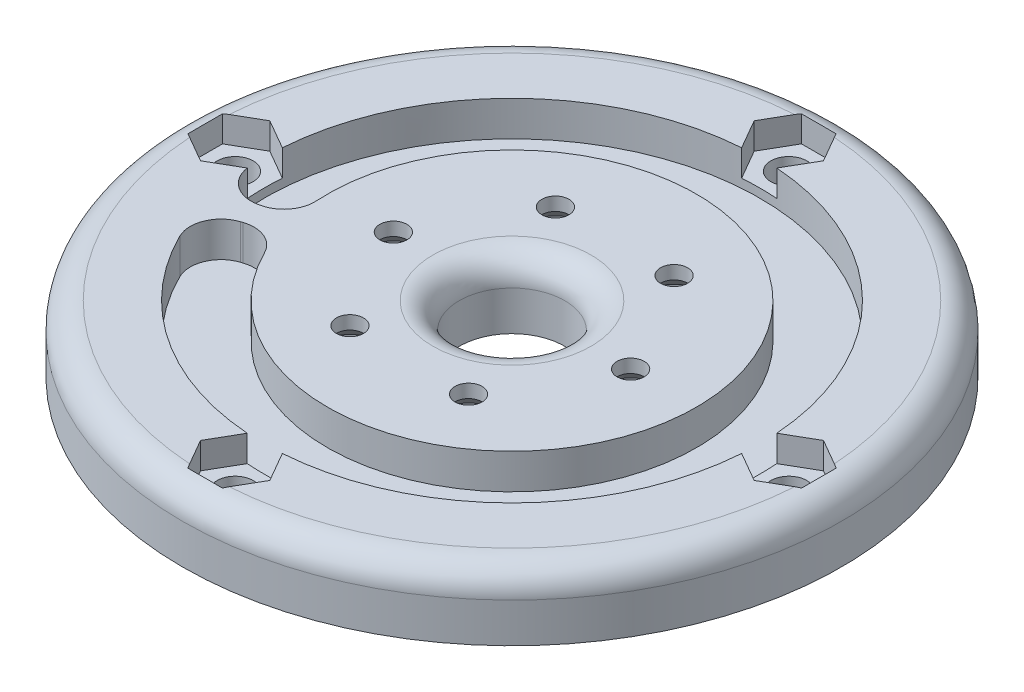
SolidWorks part; units mm, degrees
ref_plane "Front Plane" through (0, 0, 0) normal (0, 0, 1) x (1, 0, 0)
ref_plane "Top Plane" through (0, 0, 0) normal (0, 1, 0) x (1, 0, 0)
ref_plane "Right Plane" through (0, 0, 0) normal (1, 0, 0) x (0, 0, -1)
sketch "草图1" plane through (0, 0, 0) normal (0, 1, 0) x (1, 0, 0)
  circle A0 centre (0, 0) radius 37.5
  dimension "D1" = 75
extrude "凸台-拉伸1" add sketch "草图1" along normal blind 7.5
ref_axis "基准轴1" through (0, 7.5, 0) along (0, -1, 0)
sketch "草图2" plane through (0, 7.5, 0) normal (0, 1, 0) x (1, 0, 0)
  line L0 (0, 0) -> (-37.5, 0) construction
  circle A0 centre (0, 0) radius 37.5 construction
  circle A1 centre (-31.5, 0) radius 2.05
  dimension "D1" = 4.1
  dimension "D2" = 31.5
extrude "切除-拉伸1" cut sketch "草图2" against normal through all
sketch "草图3" plane through (0, 7.5, 0) normal (0, 1, 0) x (1, 0, 0)
  line L1 (-31.5, 3.944) -> (-34.9156, 1.972)
  line L2 (-34.9156, 1.972) -> (-34.9156, -1.972)
  line L3 (-34.9156, -1.972) -> (-31.5, -3.944)
  line L4 (-31.5, -3.944) -> (-28.0844, -1.972)
  line L5 (-28.0844, -1.972) -> (-28.0844, 1.972)
  line L6 (-28.0844, 1.972) -> (-31.5, 3.944)
  circle A0 centre (-31.5, 0) radius 3.4156 construction
  dimension "D1" = 3.944
extrude "切除-拉伸2" cut sketch "草图3" against normal blind 3
pattern_circular "阵列(圆周)1" count 4 over 360 about axis through (0, 7.5, 0) along (0, -1, 0) of "切除-拉伸2", "切除-拉伸1"
sketch "草图4" plane through (0, 0, 0) normal (0, -1, 0) x (1, 0, 0)
  line L0 (0, 0) -> (-31.5, 0) construction
  circle A0 centre (-13.5, 0) radius 3.05
  dimension "D1" = 13.5
  dimension "D2" = 6.1
extrude "切除-拉伸3" cut sketch "草图4" against normal offset from surface (4.5 mm away) 3 up to face at (0, 7.5, -31.5)
sketch "草图5" plane through (0, 4.5, 0) normal (0, -1, 0) x (1, 0, 0)
  line L0 (-31.5, 0) -> (0, 0) construction
  point P4 (-13.5, 0)
  dimension "D1" = 13.5
hole_wizard "CSK for M3 Countersunk Flat Head Screw1" positions "3D草图1" profile "草图6" countersink size "M3" standard "ISO" end condition through all
sketch3d "3D草图1"
  point P0 (-13.5, 4.5, 0)
sketch "草图6" plane through (-13.5, 4.5, 0) normal (1, 0, 0) x (0, 0, -1)
  line L0 (0, 0) -> (0, 3)
  line L1 (0, 3) -> (1.54, 3)
  line L2 (1.54, 3) -> (1.54, 1.48)
  line L3 (1.54, 1.48) -> (3.02, 0)
  line L5 (3.02, 0) -> (0, 0)
  line L6 (-1.54, 1.48) -> (-3.02, 0) construction
  line L11 (0, -6.35) -> (0, 107.95) construction
  dimension "Thru Hole Dia." = 3.08
  dimension "Thru Hole Depth" = 3
  dimension "Near C'Sink Dia." = 6.04
  dimension "Near C'Sink Angle" = 90
pattern_circular "阵列(圆周)2" count 6 every 60 about axis through (0, 7.5, 0) along (0, -1, 0) of "CSK for M3 Countersunk Flat Head Screw1", "切除-拉伸3"
sketch "草图7" plane through (0, 7.5, 0) normal (0, 1, 0) x (1, 0, 0)
  circle A0 centre (0, 0) radius 21
  circle A1 centre (0, 0) radius 28.2
  dimension "D1" = 42
  dimension "D2" = 56.4
extrude "切除-拉伸4" cut sketch "草图7" against normal blind 4
sketch "草图9" plane through (0, 7.5, 0) normal (0, 1, 0) x (1, 0, 0)
  circle A0 centre (0, 0) radius 6
extrude "切除-拉伸5" cut sketch "草图9" against normal through all
sketch "草图11" plane through (0, 3.5, 0) normal (0, 1, 0) x (1, 0, 0)
  line L0 (0, 0) -> (-35.6084, -11.7597) construction
  line L5 (0, 0) -> (-36.7176, -7.62) construction
  line L8 (-35.6084, -11.7597) -> (-36.7176, -7.62)
  line L11 (-36.163, -9.6899) -> (0, 0) construction
  line L14 (-20.5619, -4.2672) -> (-19.9407, -6.5854)
  line L15 (-36.7176, -7.62) -> (-20.5619, -4.2672)
  line L16 (-35.6084, -11.7597) -> (-19.9407, -6.5854)
  line L17 (-31.5, 0) -> (0, 0) construction
  circle A0 centre (0, 0) radius 37.5 construction
  circle A4 centre (0, 0) radius 21 construction
  point P5 (-20.5619, -4.2672)
  point P7 (-19.9407, -6.5854)
  dimension "D1" = 2.4
  dimension "D2" = 15
extrude "凸台-拉伸3" add sketch "草图11" along normal up to surface (4 mm away) up to face at (0, 7.5, 0)
fillet "圆角1" radius 3 1 edges at (0, 7.5, 37.5)
fillet "圆角3" radius 3 1 edges at (0, 7.5, 6)
fillet "圆角5" radius 3.5 2 edges at (-26.7775, 5.5, 8.8433) (-27.6117, 5.5, 5.7303)
fillet "圆角6" radius 3.5 2 edges at (-19.9407, 5.5, 6.5854) (-20.5619, 5.5, 4.2672)
